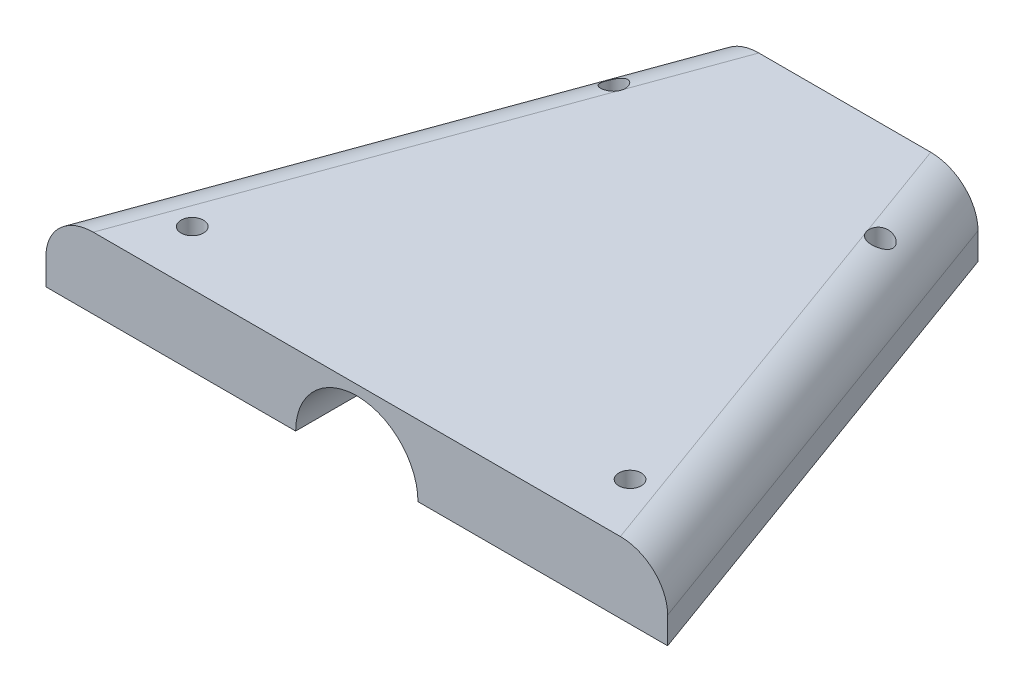
SolidWorks part; units mm, degrees
ref_plane "Front Plane" through (0, 0, 0) normal (0, 0, 1) x (1, 0, 0)
ref_plane "Top Plane" through (0, 0, 0) normal (0, 1, 0) x (1, 0, 0)
ref_plane "Right Plane" through (0, 0, 0) normal (1, 0, 0) x (0, 0, -1)
sketch "Sketch6" plane through (0, 0, 0) normal (0, 1, 0) x (1, 0, 0)
  line L0 (-16.8369, 5.7834) -> (13.1631, 5.7834)
  line L1 (13.1631, 5.7834) -> (33.1631, -49.1662)
  line L2 (33.1631, -49.1662) -> (-36.8369, -49.1662)
  line L3 (-36.8369, -49.1662) -> (-16.8369, 5.7834)
  circle A0 centre (13.1631, -5.2166) radius 1.78
  circle A1 centre (-16.8369, -5.2166) radius 1.78
  circle A2 centre (-26.4869, -43.0491) radius 1.78
  circle A3 centre (22.8131, -43.0491) radius 1.78
  dimension "D1" = 3.56
  dimension "D3" = 3.56
  dimension "D4" = 3.56
  dimension "D5" = 3.56
  dimension "D2" = 70
  dimension "D6" = 30
  dimension "D7" = 11
  dimension "D8" = 11
  dimension "D9" = 49.3
  dimension "D10" = 10.35
  dimension "D11" = 10.35
  dimension "D12" = 30
extrude "Boss-Extrude3" add sketch "Sketch6" along normal blind 8 contours L3 L0 L1 L2
sketch "Sketch8" plane through (0, 0, 49.1662) normal (0, 0, 1) x (1, 0, 0)
  line L0 (33.1631, 0) -> (-36.8369, 0) construction
  circle A0 centre (-1.8369, 0) radius 6.8846
extrude "Cut-Extrude3" cut sketch "Sketch8" against normal blind 88
sketch "Sketch9" plane through (0, 8, 0) normal (0, 1, 0) x (1, 0, 0)
  point P0 (-16.8369, -5.2166)
  point P1 (13.1631, -5.2166)
  point P3 (22.8131, -43.0491)
  point P5 (-26.4869, -43.0491)
hole_wizard "#39 (0.0995) Diameter Hole1" positions "3DSketch2" profile "Sketch11" hole size "#39" standard "ANSI Inch" end condition through all
sketch3d "3DSketch2"
  point P0 (-16.8369, 0, 5.2166)
  point P3 (13.1631, 0, 5.2166)
  point P6 (22.8131, 0, 43.0491)
  point P9 (-26.4869, 0, 43.0491)
  point P13 (22.8131, 8, 43.0491)
  point P16 (-26.4869, 8, 43.0491)
  point P19 (-16.8369, 8, 5.2166)
  point P22 (13.1631, 8, 5.2166)
sketch "Sketch11" plane through (13.1631, 8, 5.2166) normal (1, 0, 0) x (0, 0, 1)
  line L0 (0, 0) -> (0, 8)
  line L1 (0, 8) -> (1.2636, 8)
  line L2 (1.2636, 8) -> (1.2636, 0)
  line L5 (1.2636, 0) -> (0, 0)
  line L11 (0, -6.35) -> (0, 107.95) construction
  dimension "Thru Hole Dia." = 2.5273
  dimension "Thru Hole Depth" = 8
fillet "Fillet1" radius 5 2 edges at (-26.8369, 8, 21.6914) (23.1631, 8, 21.6914)
